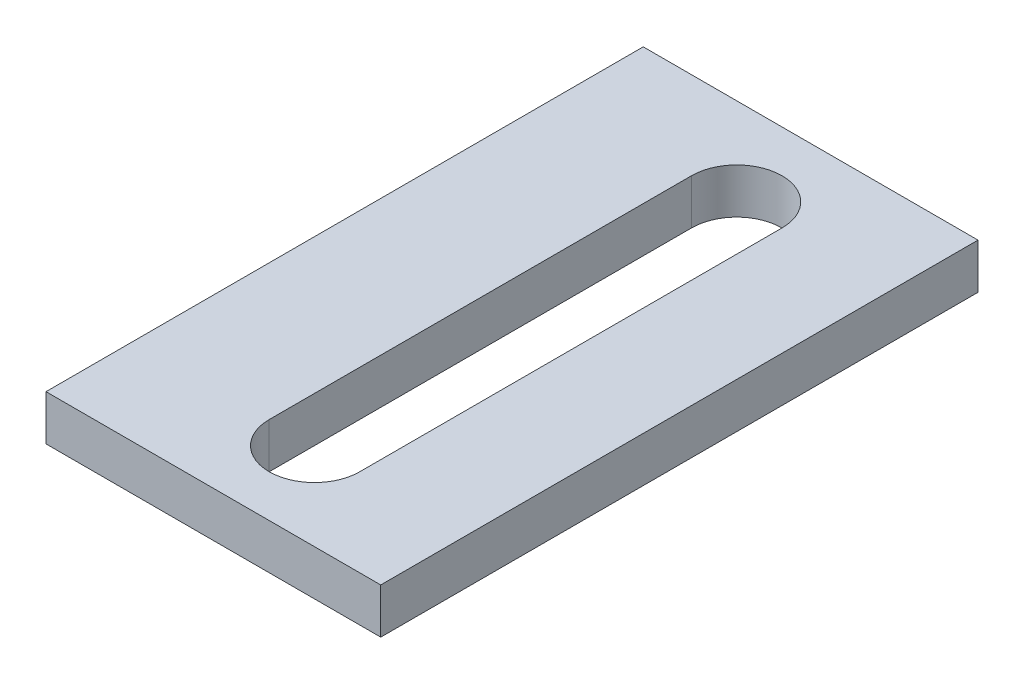
SolidWorks part; units mm, degrees
ref_plane "Front Plane" through (0, 0, 0) normal (0, 0, 1) x (1, 0, 0)
ref_plane "Top Plane" through (0, 0, 0) normal (0, 1, 0) x (1, 0, 0)
ref_plane "Right Plane" through (0, 0, 0) normal (1, 0, 0) x (0, 0, -1)
sketch "Sketch1" plane through (0, 0, 0) normal (1, 0, 0) x (0, 0, -1)
  line L1 (-6.9, -4.4) -> (6.9, -4.4)
  line L2 (-6.9, -4.4) -> (-6.9, 4.4)
  line L3 (-6.9, 4.4) -> (6.9, 4.4)
  line L4 (6.9, -4.4) -> (6.9, 4.4)
  line L5 (-6.9, -4.4) -> (6.9, 4.4) construction
  line L6 (-6.9, 4.4) -> (6.9, -4.4) construction
  point P0 (0, 0)
  dimension "D1" = 13.8
  dimension "D2" = 8.8
extrude "Boss-Extrude1" add sketch "Sketch1" along normal blind 3
sketch "Sketch2" plane through (3, 0, 0) normal (1, 0, 0) x (0, 0, -1)
  line L0 (6.9, 4.4) -> (-6.9, 4.4) construction
  line L1 (1, 4.4) -> (-1, 4.4)
  line L2 (1, 4.4) -> (1, -30.6)
  line L3 (1, -30.6) -> (-1, -30.6)
  line L4 (-1, 4.4) -> (-1, -30.6)
  line L5 (-6.9, -4.4) -> (6.9, -4.4) construction
  line L6 (-6.9, -4.4) -> (6.9, -4.4) construction
  point P8 (0, -4.4)
  point P9 (0, -30.6)
  dimension "D1" = 2
  dimension "D2" = 26.2
extrude "Boss-Extrude2" add sketch "Sketch2" along normal blind 3
sketch "Sketch3" plane through (6, 0, 0) normal (1, 0, 0) x (0, 0, -1)
  line L1 (-0.6, -30.6) -> (0.6, -30.6)
  line L2 (-0.6, -30.6) -> (-0.6, -24.6)
  line L3 (-0.6, -24.6) -> (0.6, -24.6)
  line L4 (0.6, -30.6) -> (0.6, -24.6)
  line L5 (-1, -30.6) -> (1, -30.6) construction
  point P10 (0, -30.6)
  point P11 (0, -30.6)
  dimension "D1" = 1.2
  dimension "D2" = 6
extrude "Boss-Extrude3" add sketch "Sketch3" along normal blind 7
fillet "Fillet3" radius 10 1 edges at (3, -4.4, 0)
sketch "Sketch5" plane through (0, 4.4, 0) normal (0, 1, 0) x (1, 0, 0)
  line L0 (3, 6.9) -> (0, 6.9) construction
  line L1 (3, -6.9) -> (-12, -6.9)
  line L2 (3, -6.9) -> (3, 6.9)
  line L3 (3, 6.9) -> (-12, 6.9)
  line L4 (-12, -6.9) -> (-12, 6.9)
  dimension "D1" = 15
extrude "Boss-Extrude4" add sketch "Sketch5" along normal blind 4
sketch "Sketch6" plane through (0, 4.4, 0) normal (0, -1, 0) x (1, 0, 0)
  line L0 (-6, 3) -> (-6, -3) construction
  line L1 (0, -6.9) -> (0, 6.9) construction
  circle A0 centre (-6, 3) radius 1.5
  circle A1 centre (-6, -3) radius 1.5
  point P4 (0, 0)
  point P7 (-6, 0)
  dimension "D1" = 3
  dimension "D2" = 6
  dimension "D3" = 6
extrude "Cut-Extrude4" cut sketch "Sketch6" against normal through all
sketch "Sketch8" plane through (0, 0, -1) normal (0, 0, -1) x (-1, 0, 0)
  line L0 (-3, -18.7582) -> (0, -4.4)
  line L1 (-3, -30.6) -> (-3, -11.5414) construction
  line L2 (0, -4.4) -> (-3, -4.4)
  line L3 (-3, -4.4) -> (-3, -18.7582)
extrude "Boss-Extrude5" add sketch "Sketch8" against normal up to surface (2 mm away) up to face at (3.5314, -10.3485, 1)
chamfer "Chamfer2" distance 3 angle 45 1 edges at (3, 4.4, 0)
sketch "Sketch11" plane through (0, 0, -0.6) normal (0, 0, -1) x (-1, 0, 0)
  line L0 (-6, -24.6) -> (-13, -24.6)
  line L1 (-13, -24.6) -> (-6, 1.7425)
  line L2 (-6, 1.7425) -> (-6, -24.6)
extrude "Boss-Extrude7" add sketch "Sketch11" against normal up to surface (1.2 mm away) up to face at (9.5, -27.6, 0.6)
sketch "Sketch12" plane through (0, 0, -6.9) normal (0, 0, -1) x (-1, 0, 0)
  line L0 (-3, -4.4) -> (-3, 8.4) construction
  line L1 (12, 8.4) -> (-3, 8.4)
  line L2 (12, 8.4) -> (12, 4.4)
  line L3 (12, 4.4) -> (-3, 4.4)
  line L4 (-3, 8.4) -> (-3, 4.4)
  line L5 (0, 4.4) -> (12, 4.4) construction
extrude "Boss-Extrude8" add sketch "Sketch12" along normal blind 3
sketch "Sketch13" plane through (0, 0, 6.9) normal (0, 0, 1) x (1, 0, 0)
  line L0 (3, 8.4) -> (3, -4.4) construction
  line L1 (-12, 8.4) -> (3, 8.4)
  line L2 (-12, 8.4) -> (-12, 4.4)
  line L3 (-12, 4.4) -> (3, 4.4)
  line L4 (3, 8.4) -> (3, 4.4)
  line L5 (-12, 4.4) -> (0, 4.4) construction
extrude "Boss-Extrude9" add sketch "Sketch13" along normal blind 3
sketch "Sketch14" plane through (0, 8.4, 0) normal (0, 1, 0) x (1, 0, 0)
  line L0 (-6, 3) -> (-6, -3) construction
  line L2 (-7.5, 7) -> (-7.5, -7)
  line L4 (-4.5, 7) -> (-4.5, -7)
  arc A0 (-7.5, 7) -> (-4.5, 7) centre (-6, 7) cw
  arc A1 (-4.5, -7) -> (-7.5, -7) centre (-6, -7) cw
  point P8 (-6, 0)
  point P10 (-4.5, 0)
  dimension "D1" = 3
  dimension "D2" = 14
extrude "Cut-Extrude7" cut sketch "Sketch14" against normal through all both and the other way through all
sketch "Sketch15" plane through (0, -30.6, 0) normal (0, -1, 0) x (1, 0, 0)
  line L0 (13, 0.6) -> (13, -0.6) construction
  line L1 (13, 0.32) -> (12.1921, 0.32)
  line L2 (13, 0.32) -> (13, -0.32)
  line L3 (13, -0.32) -> (12.1921, -0.32)
  line L4 (12.1921, 0.32) -> (12.1921, -0.32)
  line L5 (11.9922, 0.6) -> (11.9922, -0.6) construction
  line L6 (13, 0.6) -> (6, 0.6) construction
  line L7 (13, -0.6) -> (6, -0.6) construction
  point P13 (13, 0)
  point P14 (11.9922, 0)
  dimension "D1" = 0.28
extrude "Cut-Extrude8" cut sketch "Sketch15" against normal through all both and the other way through all
sketch "Sketch16" plane through (12.1921, 0, 0) normal (1, 0, 0) x (0, 0, -1)
  line L0 (0.32, -21.5597) -> (0.32, -30.6) construction
  line L1 (-0.32, -30.6) -> (0.32, -30.6)
  line L2 (-0.32, -30.6) -> (-0.32, -30)
  line L3 (-0.32, -30) -> (0.32, -30)
  line L4 (0.32, -30.6) -> (0.32, -30)
  dimension "D1" = 0.6
extrude "Cut-Extrude9" cut sketch "Sketch16" against normal through all both and the other way through all
chamfer "Chamfer3" distance 1 angle 45 1 edges at (12.1921, -30, 0)
sketch "Sketch17" plane through (0, 4.4, 0) normal (0, -1, 0) x (1, 0, 0)
  line L1 (20.8467, 21.9752) -> (-20.8467, 21.9752)
  line L2 (20.8467, 21.9752) -> (20.8467, -21.9752)
  line L3 (20.8467, -21.9752) -> (-20.8467, -21.9752)
  line L4 (-20.8467, 21.9752) -> (-20.8467, -21.9752)
  line L5 (20.8467, 21.9752) -> (-20.8467, -21.9752) construction
  line L6 (20.8467, -21.9752) -> (-20.8467, 21.9752) construction
sketch "Sketch18" plane through (0, 0, 9.9) normal (0, 0, 1) x (1, 0, 0)
  line L0 (3, 8.4) -> (-12, 8.4) construction
  line L1 (-0.9029, 8.4) -> (19.7991, 8.4)
  line L2 (-0.9029, 8.4) -> (-0.9029, -33.328)
  line L3 (-0.9029, -33.328) -> (19.7991, -33.328)
  line L4 (19.7991, 8.4) -> (19.7991, -33.328)
extrude "Cut-Extrude10" cut sketch "Sketch18" against normal blind 36
sketch "Sketch19" plane through (0, 4.4, 0) normal (0, -1, 0) x (1, 0, 0)
  line L0 (-0.9029, -9.9) -> (-0.9029, 9.9) construction
  line L1 (-12, -9.9) -> (-0.9029, -9.9)
  line L2 (-12, -9.9) -> (-12, 11.0285)
  line L3 (-12, 11.0285) -> (-0.9029, 11.0285)
  line L4 (-0.9029, -9.9) -> (-0.9029, 11.0285)
extrude "Cut-Extrude11" cut sketch "Sketch19" against normal blind 2.5
